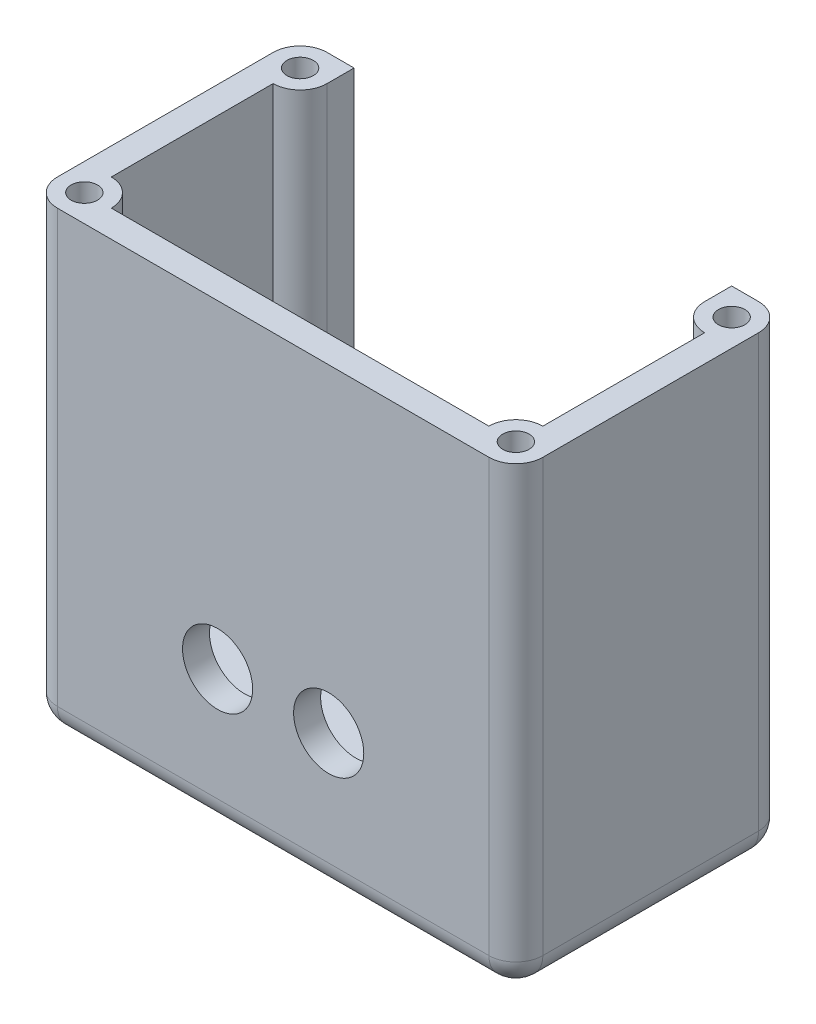
SolidWorks part; units mm, degrees
ref_plane "Front Plane" through (0, 0, 0) normal (0, 0, 1) x (1, 0, 0)
ref_plane "Top Plane" through (0, 0, 0) normal (0, 1, 0) x (1, 0, 0)
ref_plane "Right Plane" through (0, 0, 0) normal (1, 0, 0) x (0, 0, -1)
sketch "Sketch1" plane through (0, 0, 0) normal (0, 1, 0) x (1, 0, 0)
  line L1 (-57.15, 57.15) -> (57.15, 57.15)
  line L2 (-57.15, 57.15) -> (-57.15, -57.15)
  line L3 (-57.15, -57.15) -> (57.15, -57.15)
  line L4 (57.15, 57.15) -> (57.15, -57.15)
  point P4 (0, 57.15)
  point P7 (-57.15, 0)
  dimension "D1" = 114.3
  dimension "D2" = 114.3
extrude "Boss-Extrude1" add sketch "Sketch1" along normal mid plane 107.95
sketch "Sketch2" plane through (0, 53.975, 0) normal (0, 1, 0) x (1, 0, 0)
  line L1 (-50.8, 50.8) -> (50.8, 50.8)
  line L2 (-50.8, 50.8) -> (-50.8, -50.8)
  line L3 (-50.8, -50.8) -> (50.8, -50.8)
  line L4 (50.8, 50.8) -> (50.8, -50.8)
  arc A0 (-50.8, 44.45) -> (-44.45, 50.8) centre (-50.8, 50.8) ccw
  arc A1 (44.45, 50.8) -> (50.8, 44.45) centre (50.8, 50.8) ccw
  arc A2 (-50.8, -44.45) -> (-44.45, -50.8) centre (-50.8, -50.8) cw
  arc A3 (44.45, -50.8) -> (50.8, -44.45) centre (50.8, -50.8) cw
  point P4 (0, 50.8)
  point P5 (50.8, 0)
  dimension "D3" = 6.35
  dimension "D4" = 6.35
  dimension "D5" = 6.35
  dimension "D6" = 6.35
  dimension "D1" = 101.6
  dimension "D2" = 101.6
extrude "Cut-Extrude1" cut sketch "Sketch2" against normal blind 101.6 contours L3 A3 L4 A1 L1 A0 L2 A2 region at (0, 53.975, 0)
hole_wizard "CBORE for #0 Binding Head Machine Screw1" positions "3DSketch2" profile "Sketch4" counterbore size "#0" standard "ANSI Inch"
sketch3d "3DSketch2"
  point P0 (-50.8, 53.975, -50.8)
  point P3 (50.8, 53.975, -50.8)
  point P6 (-50.8, 53.975, 50.8)
  point P9 (50.8, 53.975, 50.8)
sketch "Sketch4" plane through (-50.8, 53.975, -50.8) normal (1, 0, 0) x (0, 0, 1)
  line L0 (0, 0) -> (0, 18.288)
  line L1 (0, 18.288) -> (0.9271, 17.7309)
  line L2 (0.9271, 17.7309) -> (0.9271, 9.144)
  line L3 (0.9271, 9.144) -> (3.1115, 9.144)
  line L4 (3.1115, 9.144) -> (3.1115, 0)
  line L5 (3.1115, 0) -> (0, 0)
  line L10 (0, 18.288) -> (-0.9271, 17.7309) construction
  line L11 (0, -6.35) -> (0, 107.95) construction
  dimension "Hole Dia." = 1.8542
  dimension "Hole Depth" = 18.288
  dimension "C'Bore Dia." = 6.223
  dimension "C'Bore Depth" = 9.144
  dimension "Drill Angle" = 118
sketch "Sketch5" plane through (0, 0, -50.8) normal (0, 0, 1) x (1, 0, 0)
  line L0 (7.625, 3.185) -> (-7.625, 3.185) construction
  line L1 (-17.47, 20.655) -> (17.47, 20.655)
  line L2 (-17.47, 20.655) -> (-17.47, -14.285)
  line L3 (-17.47, -14.285) -> (17.47, -14.285)
  line L4 (17.47, 20.655) -> (17.47, -14.285)
  line L5 (-7.625, 10.81) -> (7.625, 10.81)
  line L6 (-7.625, 10.81) -> (-7.625, -4.44)
  line L7 (-7.625, -4.44) -> (7.625, -4.44)
  line L8 (7.625, 10.81) -> (7.625, -4.44)
  line L9 (-44.45, -47.625) -> (44.45, -47.625) construction
  line L10 (-57.15, 53.975) -> (-57.15, -53.975) construction
  line L11 (0, 10.81) -> (0, -4.44) construction
  point P8 (0, 10.81)
  point P9 (0, 20.655)
  point P12 (17.47, 3.185)
  point P13 (7.625, 3.185)
  dimension "D1" = 34.94
  dimension "D2" = 15.25
  dimension "D3" = 15.25
  dimension "D4" = 34.94
  dimension "D5" = 39.68
  dimension "D6" = 33.34
extrude "Cut-Extrude5" cut sketch "Sketch5" against normal blind 0.55
extrude "Cut-Extrude6" cut sketch "Sketch5<3>" against normal up to next contours L8 L5 L6 L7 | L6 L5 region at (0, 3.185, -50.8)
sketch "Sketch5<3>" plane through (0, 0, -50.8) normal (0, 0, 1) x (1, 0, 0) same geometry as "Sketch5"
sketch "Sketch13" plane through (0, 0, -57.15) normal (0, 0, -1) x (-1, 0, 0)
  line L0 (-57.15, 53.975) -> (57.15, 53.975) construction
  line L1 (-57.15, 53.975) -> (-57.15, -53.975) construction
  line L2 (57.15, 53.975) -> (57.15, -53.975) construction
  line L3 (-14.2875, 27.94) -> (-14.2875, 22.86) construction
  line L4 (14.2875, 22.86) -> (14.2875, 27.94) construction
  line L5 (13.7875, 29.177) -> (13.7875, 21.623)
  line L6 (14.7875, 29.177) -> (14.7875, 21.623)
  line L7 (11.5934, 22.7059) -> (16.9816, 28.0941)
  line L8 (11.5934, 28.0941) -> (16.9816, 22.7059)
  circle A0 centre (-14.2875, 25.4) radius 2.54
  circle A1 centre (14.2875, 25.4) radius 2.54
  circle A2 centre (14.2875, 25.4) radius 3.81
  point P19 (13.7875, 25.4)
  point P20 (14.7875, 25.4)
  dimension "D1" = 5.08
  dimension "D2" = 5.08
  dimension "D7" = 7.62
  dimension "D3" = 28.575
  dimension "D4" = 28.575
  dimension "D5" = 42.8625
  dimension "D6" = 42.8625
  dimension "D8" = 1
  dimension "D9" = 0.5
  dimension "D10" = 45
  dimension "D11" = 45
extrude "Boss-Extrude2" add sketch "Sketch13" along normal blind 1.27 contours A0
ref_plane "Plane1" through (14.2875, 25.4, -57.15) normal (0, -1, 0) x (-1, 0, 0)
sketch "Sketch14" plane through (14.2875, 25.4, -57.15) normal (0, -1, 0) x (-1, 0, 0)
  line L0 (0, 1.27) -> (0, 2.54)
  line L1 (2.54, 1.27) -> (-2.54, 1.27) construction
  line L2 (0, 2.54) -> (2.286, 2.54)
  line L3 (2.286, 2.54) -> (2.64, 1.905)
  line L4 (2.64, 1.905) -> (2.64, 1.27)
  line L5 (2.64, 1.27) -> (2.54, 1.27)
  line L6 (2.54, 0) -> (2.54, 1.27) construction
  line L7 (2.54, 1.27) -> (0, 1.27)
  dimension "D1" = 1.27
  dimension "D2" = 0.1
  dimension "D3" = 2.286
  dimension "D4" = 0.635
revolve "Revolve1" add sketch "Sketch14" angle 360 about L0
ref_plane "Plane2" through (-14.2875, 25.4, -57.15) normal (0, -1, 0) x (-1, 0, 0)
extrude "Cut-Extrude7" cut sketch "Sketch13<4>" against normal blind 2.54 contours L8 A1 L7 L6 | L6 A1 L8 | L5 A1 L6 L8 L7 | L7 A1 L6 | L6 A1 L5 L8 L7 | L7 L8 L6 | L8 L5 L7 | L8 A1 L7 L5 | L7 A1 L5 | L5 A1 L8 region at (-14.2875, 26.7822, -57.15) region at (-13.3374, 27.0404, -57.15) region at (-13.9542, 25.4, -57.15) region at (-12.7011, 25.4, -57.15) region at (-15.2376, 27.0404, -57.15) region at (-14.2875, 24.0178, -57.15) region at (-13.3374, 23.7596, -57.15) region at (-14.6208, 25.4, -57.15) region at (-15.8739, 25.4, -57.15) region at (-15.2376, 23.7596, -57.15)
sketch "Sketch13<4>" plane through (0, 0, -57.15) normal (0, 0, -1) x (-1, 0, 0) same geometry as "Sketch13"
extrude "Cut-Extrude8" cut sketch "Sketch13<5>" against normal blind 0.635 contours L7 A2 L5 A1 | L6 A2 L8 A1 | L7 A2 L6 A1 | L5 A2 L8 A1 region at (-12.8483, 28.2299, -57.15) region at (-15.7267, 28.2299, -57.15) region at (-12.8483, 22.5701, -57.15) region at (-15.7267, 22.5701, -57.15)
sketch "Sketch13<5>" plane through (0, 0, -57.15) normal (0, 0, -1) x (-1, 0, 0) same geometry as "Sketch13"
extrude "Cut-Extrude9" cut sketch "Sketch13<6>" against normal blind 1.27 contours L6 A2 L5 A1 | L5 A2 L6 A1 region at (-14.2875, 28.5612, -57.15) region at (-14.2875, 22.2388, -57.15)
sketch "Sketch13<6>" plane through (0, 0, -57.15) normal (0, 0, -1) x (-1, 0, 0) same geometry as "Sketch13"
sketch "Sketch17" plane through (-14.2875, 25.4, -57.15) normal (0, -1, 0) x (-1, 0, 0)
  line L0 (0, -1.27) -> (0, -2.54)
  line L1 (0.5, -1.27) -> (-0.5, -1.27) construction
  line L2 (0, -2.54) -> (2.286, -2.54)
  line L3 (2.286, -2.54) -> (2.64, -1.905)
  line L7 (2.54, -1.27) -> (0, -1.27)
  line L8 (2.64, -1.905) -> (2.64, -1.27)
  line L9 (2.64, -1.27) -> (2.54, -1.27)
  dimension "D1" = 2.54
  dimension "D2" = 2.286
  dimension "D3" = 0.1
  dimension "D4" = 1.27
  dimension "D5" = 0.635
revolve "Cut-Revolve1" cut sketch "Sketch17" angle 360 about L0
ref_plane "Plane3" through (0, 3.185, 0) normal (0, -1, 0) x (0, 0, 1)
ref_axis "Axis1" through (0, 3.185, 62.992) along (0, 0, -1)
ref_axis "Axis2" through (0, 59.3725, 0) along (0, -1, 0)
sketch "Sketch20" plane through (0, 0, -57.15) normal (0, 0, -1) x (-1, 0, 0)
  line L1 (-13.97, 17.155) -> (13.97, 17.155)
  line L2 (-13.97, 17.155) -> (-13.97, -10.785)
  line L3 (-13.97, -10.785) -> (13.97, -10.785)
  line L4 (13.97, 17.155) -> (13.97, -10.785)
  point P4 (0, 17.155)
  point P9 (13.97, 3.185)
  dimension "D1" = 27.94
  dimension "D2" = 27.94
hole_wizard "CBORE for M5 Hex Head Bolt2" positions "3DSketch4" profile "Sketch21" counterbore size "M5" standard "ANSI Metric"
sketch3d "3DSketch4"
  point P0 (13.97, 17.155, -57.15)
  point P3 (-13.97, 17.155, -57.15)
  point P6 (-13.97, -10.785, -57.15)
  point P9 (13.97, -10.785, -57.15)
sketch "Sketch21" plane through (13.97, 17.155, -57.15) normal (1, 0, 0) x (0, 1, 0)
  line L0 (0, 0) -> (0, 18.288)
  line L1 (0, 18.288) -> (2.75, 16.6356)
  line L2 (2.75, 16.6356) -> (2.75, 5.8)
  line L3 (2.75, 5.8) -> (2.25, 5.8)
  line L4 (2.25, 5.8) -> (2.25, 0)
  line L5 (2.25, 0) -> (0, 0)
  line L10 (0, 18.288) -> (-2.75, 16.6356) construction
  line L11 (0, -6.35) -> (0, 107.95) construction
  dimension "Hole Dia." = 5.5
  dimension "Hole Depth" = 18.288
  dimension "C'Bore Dia." = 4.5
  dimension "C'Bore Depth" = 5.8
  dimension "Drill Angle" = 118
sketch "Sketch23" plane through (0, 0, -59.69) normal (0, 0, -1) x (-1, 0, 0)
  line L0 (-14.7875, 27.9922) -> (-14.7875, 22.8078)
  line L1 (-13.7875, 27.9922) -> (-13.7875, 22.8078)
  line L2 (-14.2875, 28.04) -> (-14.2875, 22.76) construction
  circle A0 centre (-14.2875, 25.4) radius 2.64 construction
  circle A1 centre (-14.2875, 25.4) radius 2.64
  circle M1 centre (-14.2875, 25.4) radius 2.286
  dimension "D1" = 5.28
  dimension "D2" = 0.5
  dimension "D3" = 0.5
extrude "Cut-Extrude10" cut sketch "Sketch23" against normal blind 2.032 contours L2 L0 M1 | L2 L1 M1 | L2 A1 L0 M1 | A1 L2 L1 M1 | L2 A1 L1 M1 | L2 L0 A1 M1 region at (14.5384, 27.8458, -59.69) region at (14.5365, 25.4, -59.69) region at (14.0366, 27.8458, -59.69) region at (14.5384, 22.9542, -59.69) region at (14.0385, 25.4, -59.69) region at (14.0366, 22.9542, -59.69)
pattern_circular "CirPattern1" count 4 every 90 about axis through (0, 3.185, 62.992) along (0, 0, -1) of "Boss-Extrude2", "Revolve1", "Cut-Extrude7", "Cut-Extrude8", "Cut-Extrude9", "Cut-Revolve1", "Cut-Extrude10"
sketch "Sketch24" plane through (0, 0, 57.15) normal (0, 0, 1) x (1, 0, 0)
  line L1 (-57.15, 53.975) -> (57.15, 53.975)
  line L2 (-57.15, 53.975) -> (-57.15, -53.975)
  line L3 (-57.15, -53.975) -> (57.15, -53.975)
  line L4 (57.15, 53.975) -> (57.15, -53.975)
extrude "Cut-Extrude11" cut sketch "Sketch24" against normal blind 50.8
sketch "Sketch25" plane through (0, -47.625, 0) normal (0, 1, 0) x (1, 0, 0)
  line L0 (50.8, 44.45) -> (50.8, -6.35) construction
  line L1 (-50.8, -6.35) -> (50.8, -6.35)
  line L2 (-50.8, -6.35) -> (-50.8, 0)
  line L3 (-50.8, 0) -> (50.8, 0)
  line L4 (50.8, -6.35) -> (50.8, 0)
  line L5 (-50.8, 44.45) -> (-50.8, -6.35) construction
  line L6 (50.8, 44.45) -> (50.8, -6.35) construction
  line L7 (-50.8, 0) -> (-50.8, 6.35)
  line L8 (50.8, 0) -> (50.8, 6.35)
  arc A0 (-50.8, 6.35) -> (-44.45, 0) centre (-50.8, 0) cw
  arc A1 (50.8, 6.35) -> (44.45, 0) centre (50.8, 0) ccw
  line M5 (-50.8, 44.45) -> (-50.8, -6.35)
  line M6 (-50.8, -6.35) -> (50.8, -6.35)
  line M7 (50.8, -6.35) -> (50.8, 44.45)
  dimension "D2" = 6.35
  dimension "D3" = 6.35
  dimension "D1" = 6.35
extrude "Boss-Extrude3" add sketch "Sketch25" along normal blind 101.6 contours A0 L3 M5 | L3 M5 M6 M7 | A1 L3 M7 region at (0, -47.625, 3.175) region at (-48.105, -47.625, -2.695) region at (48.105, -47.625, -2.695)
sketch "Sketch26" plane through (0, 0, 6.35) normal (0, 0, 1) x (1, 0, 0)
  line L0 (-13.081, -21.1201) -> (13.081, -21.1201) construction
  line L1 (-57.15, -53.975) -> (57.15, -53.975) construction
  circle A0 centre (-13.081, -21.1201) radius 8.255
  circle A1 centre (13.081, -21.1201) radius 8.255
  point P4 (0, -21.1201)
  dimension "D1" = 16.51
  dimension "D2" = 16.51
  dimension "D3" = 26.162
  dimension "D4" = 32.8549
sketch "Sketch27" plane through (0, -47.625, 0) normal (0, 1, 0) x (1, 0, 0)
  line L0 (-44.45, 0) -> (44.45, 0) construction
  line L1 (-10.75, 35.652) -> (10.75, 35.652)
  line L2 (-10.75, 35.652) -> (-10.75, 9.652)
  line L3 (-10.75, 9.652) -> (10.75, 9.652)
  line L4 (10.75, 35.652) -> (10.75, 9.652)
  circle A0 centre (-10.75, 9.652) radius 3.81
  circle A1 centre (10.75, 9.652) radius 3.81
  circle A2 centre (10.75, 35.652) radius 3.81
  circle A3 centre (-10.75, 35.652) radius 3.81
  point P8 (0, 9.652)
  dimension "D3" = 7.62
  dimension "D4" = 7.62
  dimension "D5" = 7.62
  dimension "D6" = 7.62
  dimension "D1" = 26
  dimension "D2" = 21.5
  dimension "D7" = 9.652
extrude "Boss-Extrude4" add sketch "Sketch27" along normal blind 7.62 contours A3 | A2 | A1 | A0
extrude "Cut-Extrude12" cut sketch "Sketch26" against normal up to next
hole_wizard "CBORE for M5 Hex Head Bolt3" positions "3DSketch5" profile "Sketch28" counterbore size "M5" standard "ANSI Metric"
sketch3d "3DSketch5"
  line L0 (-10.75, -40.005, -35.652) -> (-10.75, -47.625, -35.652) construction
  line L1 (10.75, -40.005, -35.652) -> (10.75, -47.625, -35.652) construction
  line L2 (10.75, -40.005, -9.652) -> (10.75, -47.625, -9.652) construction
  line L3 (-10.75, -40.005, -9.652) -> (-10.75, -47.625, -9.652) construction
  point P0 (-10.75, -40.005, -35.652)
  point P4 (10.75, -40.005, -35.652)
  point P8 (10.75, -40.005, -9.652)
  point P12 (-10.75, -40.005, -9.652)
sketch "Sketch28" plane through (-10.75, -40.005, -35.652) normal (1, 0, 0) x (0, 0, 1)
  line L0 (0, 0) -> (0, 8.89)
  line L1 (0, 8.89) -> (1.25, 8.1389)
  line L2 (1.25, 8.1389) -> (1.25, 5.8)
  line L3 (1.25, 5.8) -> (2.225, 5.8)
  line L4 (2.225, 5.8) -> (2.225, 0)
  line L5 (2.225, 0) -> (0, 0)
  line L10 (0, 8.89) -> (-1.25, 8.1389) construction
  line L11 (0, -6.35) -> (0, 107.95) construction
  dimension "Hole Dia." = 2.5
  dimension "Hole Depth" = 8.89
  dimension "C'Bore Dia." = 4.45
  dimension "C'Bore Depth" = 5.8
  dimension "Drill Angle" = 118
hole_wizard "CBORE for #0 Binding Head Machine Screw2" positions "3DSketch6" profile "Sketch29" counterbore size "#0" standard "ANSI Inch"
sketch3d "3DSketch6"
  line L0 (57.15, 53.975, 6.35) -> (57.15, 53.975, -57.15) construction
  line L1 (57.15, 53.975, 6.35) -> (-57.15, 53.975, 6.35) construction
  line L2 (-57.15, 53.975, -57.15) -> (-57.15, 53.975, 6.35) construction
  point P0 (50.8, 53.975, 0)
  point P2 (-50.8, 53.975, 0)
  dimension "D1" = 6.35
  dimension "D2" = 6.35
  dimension "D3" = 6.35
  dimension "D4" = 6.35
sketch "Sketch29" plane through (50.8, 53.975, 0) normal (1, 0, 0) x (0, 0, 1)
  line L0 (0, 0) -> (0, 8.89)
  line L1 (0, 8.89) -> (0.9271, 8.3329)
  line L2 (0.9271, 8.3329) -> (0.9271, 9.144)
  line L3 (0.9271, 9.144) -> (3.1115, 9.144)
  line L4 (3.1115, 9.144) -> (3.1115, 0)
  line L5 (3.1115, 0) -> (0, 0)
  line L10 (0, 8.89) -> (-0.9271, 8.3329) construction
  line L11 (0, -6.35) -> (0, 107.95) construction
  dimension "Hole Dia." = 1.8542
  dimension "Hole Depth" = 8.89
  dimension "C'Bore Dia." = 6.223
  dimension "C'Bore Depth" = 9.144
  dimension "Drill Angle" = 118
fillet "Fillet1" radius 6.35 8 edges at (57.15, -53.975, -25.4) (0, -53.975, -57.15) (-57.15, -53.975, -25.4) (0, -53.975, 6.35) (57.15, 0, 6.35) (57.15, 0, -57.15) (-57.15, 0, 6.35) (-57.15, 0, -57.15)
sketch "Sketch30" plane through (0, 0, -50.8) normal (0, 0, 1) x (1, 0, 0)
  line L0 (-50.8, -53.975) -> (50.8, -53.975) construction
  line L1 (-44.45, 53.975) -> (44.45, 53.975)
  line L2 (-44.45, 53.975) -> (-44.45, -47.625)
  line L3 (-44.45, -47.625) -> (44.45, -47.625)
  line L4 (44.45, 53.975) -> (44.45, -47.625)
  line L5 (-6.35, -47.625) -> (6.35, -47.625)
  line L6 (-6.35, -47.625) -> (-6.35, -53.975)
  line L7 (-6.35, -53.975) -> (6.35, -53.975)
  line L8 (6.35, -47.625) -> (6.35, -53.975)
  point P12 (0, -53.975)
  point P13 (0, -47.625)
  line M9 (-17.47, -14.285) -> (-17.47, 20.655)
  line M10 (-17.47, 20.655) -> (17.47, 20.655)
  line M11 (17.47, 20.655) -> (17.47, -14.285)
  line M12 (17.47, -14.285) -> (-17.47, -14.285)
  line M13 (44.45, 53.975) -> (-44.45, 53.975)
  line M14 (-44.45, 53.975) -> (-44.45, -47.625)
  line M15 (-44.45, -47.625) -> (44.45, -47.625)
  line M16 (44.45, -47.625) -> (44.45, 53.975)
  dimension "D1" = 12.7
extrude "Cut-Extrude13" cut sketch "Sketch30" against normal up to next contours L3 M16 M13 M14 M15 M12 M9 M10 M11 | M9 M12 M11 M10 | L6 L7 L8 L5 region at (0, 52.625, -50.8) region at (0, 3.185, -50.8)
